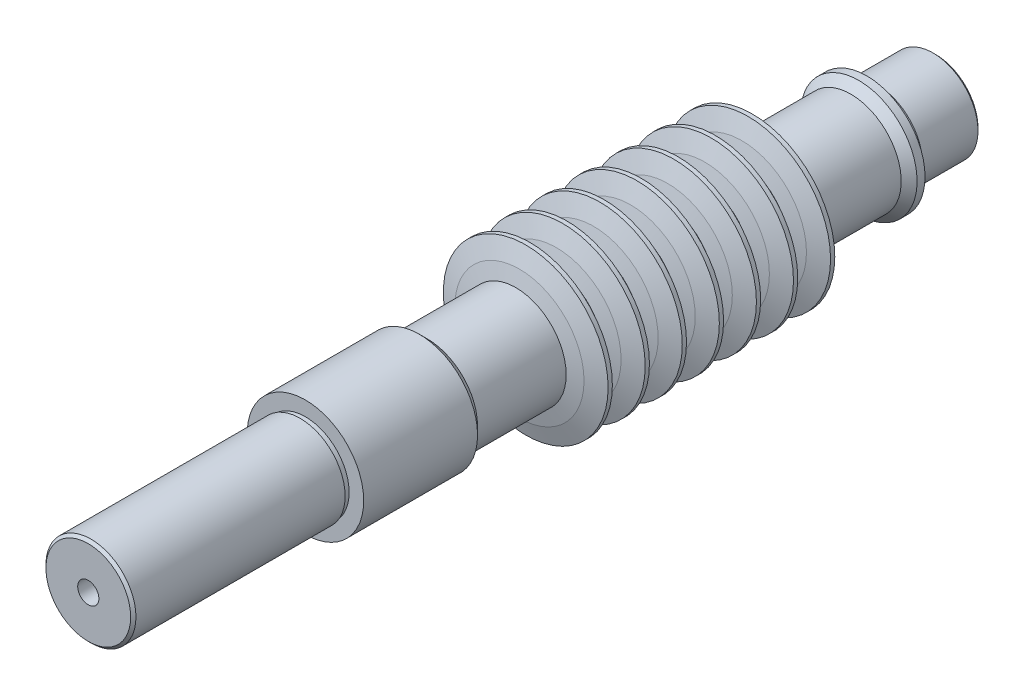
SolidWorks part; units mm, degrees
material "1023 Carbon Steel Sheet (SS)"
ref_plane "Front Plane" through (0, 0, 0) normal (0, 0, 1) x (1, 0, 0)
ref_plane "Top Plane" through (0, 0, 0) normal (0, 1, 0) x (1, 0, 0)
ref_plane "Right Plane" through (0, 0, 0) normal (1, 0, 0) x (0, 0, -1)
sketch "Sketch1" plane through (0, 0, 0) normal (0, 0, 1) x (1, 0, 0)
  circle A0 centre (0, 0) radius 8.5
  dimension "D1" = 17
extrude "Extrude1" add sketch "Sketch1" along normal blind 11
sketch "Sketch2" plane through (0, 0, 11) normal (0, 0, 1) x (1, 0, 0)
  circle A0 centre (0, 0) radius 6.5
  dimension "D1" = 13
extrude "Extrude2" add sketch "Sketch2" along normal blind 2
sketch "Sketch3" plane through (0, 0, 13) normal (0, 0, 1) x (1, 0, 0)
  circle A0 centre (0, 0) radius 11
  dimension "D1" = 22
extrude "Extrude3" add sketch "Sketch3" along normal blind 3
sketch "Sketch4" plane through (0, 0, 16) normal (0, 0, 1) x (1, 0, 0)
  circle A0 centre (0, 0) radius 9.5
  dimension "D1" = 19
extrude "Extrude4" add sketch "Sketch4" along normal blind 80
sketch "Sketch5" plane through (0, 0, 96) normal (0, 0, 1) x (1, 0, 0)
  circle A0 centre (0, 0) radius 11
  circle A1 centre (0, 0) radius 9.5 construction
  dimension "D1" = 22
extrude "Extrude5" add sketch "Sketch5" along normal blind 23
sketch "Sketch6" plane through (0, 0, 119) normal (0, 0, 1) x (1, 0, 0)
  circle A0 centre (0, 0) radius 8.25
  circle A1 centre (0, 0) radius 11 construction
  dimension "D1" = 2.75
extrude "Extrude6" add sketch "Sketch6" along normal blind 1
sketch "Sketch7" plane through (0, 0, 120) normal (0, 0, 1) x (1, 0, 0)
  circle A0 centre (0, 0) radius 8.5
  dimension "D1" = 17
extrude "Extrude7" add sketch "Sketch7" along normal blind 40
chamfer "Chamfer1" distance 0.5 angle 45 2 edges at (8.5, 0, 0) (8.5, 0, 160)
chamfer "Chamfer2" distance 1.5 angle 45 2 edges at (11, 0, 16) (11, 0, 96)
sketch "Sketch8" plane through (0, 0, 160) normal (0, 0, 1) x (1, 0, 0)
  circle A0 centre (0, 0) radius 2
  dimension "D1" = 4
extrude "Extrude8" cut sketch "Sketch8" against normal blind 6
chamfer "Chamfer3" distance 2 angle 45 1 edges at (2, 0, 154)
sketch "Sketch9" plane through (0, 0, 0) normal (0, 0, -1) x (-1, 0, 0)
  circle A0 centre (0, 0) radius 2
  circle A1 centre (0, 0) radius 2 construction
extrude "Extrude9" cut sketch "Sketch9" against normal blind 6
chamfer "Chamfer4" distance 2 angle 45 1 edges at (-2, 0, 6)
ref_plane "Plane1" through (-8.5, 0, 0) normal (1, 0, 0) x (0, 0, -1)
sketch "Sketch10" plane through (-8.5, 0, 0) normal (1, 0, 0) x (0, 0, -1)
  line L0 (0, 0) -> (-163.4069, 0) construction
  line L1 (-125, -3) -> (-139, -3)
  line L2 (-120, -8.5) -> (-120, 8.5) construction
  line L3 (-125, 3) -> (-139, 3)
  arc A0 (-139, 3) -> (-139, -3) centre (-139, 0) ccw
  arc A1 (-125, -3) -> (-125, 3) centre (-125, 0) ccw
  dimension "D2" = 20
  dimension "D1" = 6
  dimension "D3" = 2
extrude "Extrude11" cut sketch "Sketch10" along normal blind 2
ref_plane "Plane2" through (0, 0, 77) normal (0, 0, 1) x (1, 0, 0)
ref_plane "Plane4" [suppressed] through (0, 0, 32.94) normal (0, 0, -1) x (-1, 0, 0)
sketch "Sketch11" plane through (0, 0, 0) normal (0, 1, 0) x (1, 0, 0)
  line L0 (9.5, -79.265) -> (9.5, -74.735)
  line L1 (9.5, -96) -> (9.5, -16) construction
  line L2 (9.5, -74.735) -> (12.1984, -75.4096)
  line L3 (15.56, -76.6) -> (15.56, -77.4)
  line L4 (12.1984, -78.5904) -> (9.5, -79.265)
  line L5 (-12.1, -77) -> (12.1, -77) construction
  line L6 (15.56, -77) -> (9.5, -77) construction
  line L7 (0, -84.0141) -> (0, -70.9565) construction
  line L8 (15.56, -76.6) -> (12.1984, -75.4096)
  line L9 (15.56, -77.4) -> (12.1984, -78.5904)
  dimension "D1" = 28.072
  dimension "D2" = 4.53
  dimension "D3" = 6.06
  dimension "D5" = 39
  dimension "D6" = 0.8
revolve "Revolve1" add sketch "Sketch11" angle 360 about L7
sketch "Sketch12" plane through (0, 0, 0) normal (0, 1, 0) x (1, 0, 0)
  line L0 (0, -108.2571) -> (0, -33.1429) construction
pattern_linear "LPattern1" count 7 spacing 7 along (0, 0, -1) of "Revolve1"
